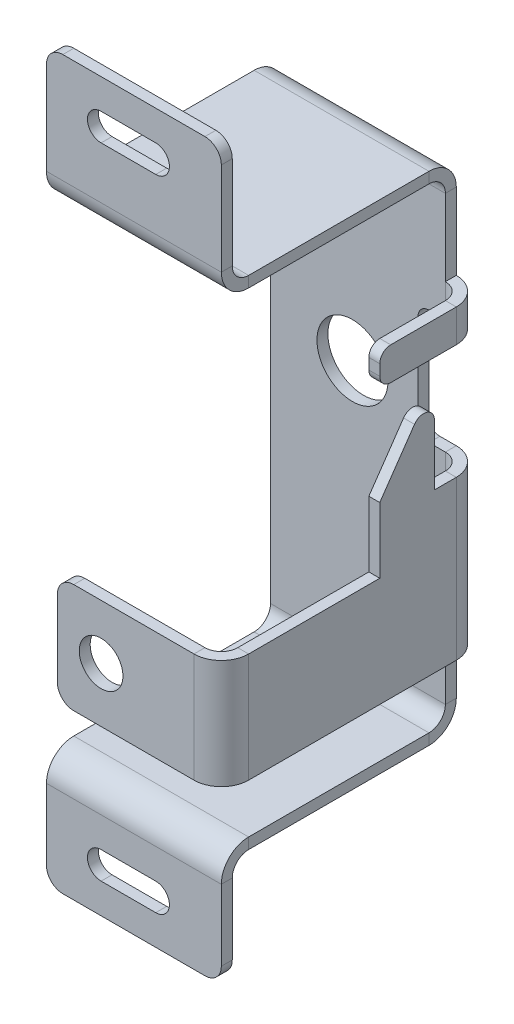
SolidWorks part; units mm, degrees
note: The reader was unsure of these and kept them because the rebuilt part matched: flange length of "Edge-Flange1", "Edge-Flange2", "Edge-Flange3", "Edge-Flange4", "Edge-Flange5", "Edge-Flange6", "Edge-Flange7".
ref_plane "Front Plane" through (0, 0, 0) normal (1, 0, 0) x (0, 1, 0)
ref_plane "Top Plane" through (0, 0, 0) normal (0, 0, 1) x (0, 1, 0)
ref_plane "Right Plane" through (0, 0, 0) normal (0, 1, 0) x (-1, 0, 0)
sketch "Sketch1" plane through (0, 0, 0) normal (0, 0, 1) x (0, 1, 0)
  line L0 (0, 74.7145) -> (0, -84.0142) construction
  line L1 (-132.9432, 0) -> (137.1703, 0) construction
  line L3 (-49, 15) -> (42, 15)
  line L4 (-49, 15) -> (-49, -17)
  line L5 (-49, -17) -> (42, -17)
  line L6 (42, 15) -> (42, -17)
  dimension "D1" = 49
  dimension "D2" = 15
  dimension "D3" = 17
  dimension "D4" = 42
base flange "Base-Flange1" sketch "Sketch1" thickness 2 reverse thickness direction yes parameters "D1"=0.25
edge flange "Edge-Flange1" sketch "Sketch8" flange angle 90 flange length 43 flange position material inside bend radius 3 thickness 2 relief rectangular parameters "D6"=10
sketch "Sketch8" plane through (0, -49, 2) normal (0, -1, 0) x (1, 0, 0)
  line L2 (-15, 0) -> (-15, 41)
  line L3 (-15, 41) -> (17, 41)
  line L4 (17, 41) -> (17, 0)
  line L7 (-15, 0) -> (17, 0) construction
  line L8 (-15, 0) -> (17, 0)
bend "EdgeBend1" bend radius 3 bend angle 90 parameters "D5"=1
edge flange "Edge-Flange2" sketch "Sketch11" flange angle 90 flange length 21 flange position material inside bend radius 3 thickness 2 relief rectangular parameters "D6"=10
sketch "Sketch11" plane through (0, -49, 43) normal (0, 0, 1) x (-1, 0, 0)
  line L0 (-17, 0) -> (15, 0) construction
  line L1 (-17, 0) -> (15, 0)
  line L2 (-17, 0) -> (-17, 19)
  line L3 (-17, 19) -> (15, 19)
  line L4 (15, 19) -> (15, 0)
bend "EdgeBend2" bend radius 3 bend angle 90 parameters "D5"=2
fillet "Fillet1" radius 3 2 edges at (-15, -68, 42) (17, -68, 42)
edge flange "Edge-Flange3" sketch "Sketch14" flange angle 90 flange length 43 flange position bend outside bend radius 3 thickness 2 relief rectangular parameters "D6"=10
sketch "Sketch14" plane through (17, 0, 2) normal (1, 0, 0) x (0, 1, 0)
  line L0 (-33, 0) -> (-4, 0)
  line L2 (-33, 0) -> (-33, 41)
  line L3 (-33, 41) -> (-13, 41)
  line L4 (-13, 41) -> (-13, 17)
  line L5 (-44, -2) -> (42, -2) construction
  line L6 (-49, 3) -> (-49, 36) construction
  line L7 (-4, 7) -> (7.0902, 7)
  line L8 (8.2246, 10.6472) -> (-1, 17)
  line L9 (-1, 17) -> (-13, 17)
  line L10 (2, 56.666) -> (2, -14.644) construction
  line L11 (-4, 7) -> (-4, 0)
  line L12 (-44, 0) -> (42, 0) construction
  line L13 (-68, 39) -> (-68, 41) construction
  arc A0 (7.0902, 7) -> (8.2246, 10.6472) centre (7.0902, 9) ccw
  point P1 (9, 8.406)
  dimension "D9" = 2
  dimension "D1" = 43
  dimension "D2" = 16
  dimension "D3" = 20
  dimension "D4" = 6
  dimension "D5" = 10
  dimension "D6" = 13
  dimension "D7" = 10
  dimension "D8" = 9
  dimension "D10" = 70
bend "EdgeBend3" bend radius 3 bend angle 90 parameters "D5"=3
edge flange "Edge-Flange4" sketch "Sketch17" flange angle 90 flange length 30 flange position bend outside bend radius 3 thickness 2 relief rectangular parameters "D6"=10
sketch "Sketch17" plane through (20, 0, 43) normal (0, 0, 1) x (0, 1, 0)
  line L0 (-13, 0) -> (-33, 0) construction
  line L1 (-13, 0) -> (-33, 0)
  line L2 (-33, 0) -> (-33, 25)
  line L3 (-30, 28) -> (-16, 28)
  line L4 (-13, 25) -> (-13, 0)
  line L5 (-13, -2) -> (-33, -2) construction
  arc A0 (-16, 28) -> (-13, 25) centre (-16, 25) cw
  arc A1 (-33, 25) -> (-30, 28) centre (-30, 25) cw
  circle A2 centre (-23, 20) radius 4
  point P13 (-23, 28)
  dimension "D2" = 3
  dimension "D3" = 8
  dimension "D1" = 30
  dimension "D4" = 22
bend "EdgeBend4" bend radius 3 bend angle 90 parameters "D5"=4
sketch "Sketch18" plane through (0, 0, 2) normal (0, 0, 1) x (1, 0, 0)
  line L0 (-15, 42) -> (-15, -44) construction
  line L1 (-12, -68) -> (14, -68) construction
  line L2 (17, -4) -> (14, -4)
  line L3 (12, -2) -> (12, 15)
  line L4 (14, 17) -> (17, 17)
  line L5 (17, -4) -> (17, 42) construction
  line L6 (0, 2) -> (17, 2) construction
  line L7 (17, 17) -> (17, -4)
  circle A0 centre (0, 2) radius 6.5
  arc A1 (12, 15) -> (14, 17) centre (14, 15) cw
  arc A2 (14, -4) -> (12, -2) centre (14, -2) cw
  dimension "D1" = 13
  dimension "D6" = 2
  dimension "D2" = 15
  dimension "D3" = 70
  dimension "D4" = 12
  dimension "D5" = 15
extrude "Cut-Extrude1" cut sketch "Sketch18" against normal blind 10 normal cut yes
edge flange "Edge-Flange5" sketch "Sketch21" flange angle 90 flange length 19 flange position bend outside bend radius 3 thickness 2 relief rectangular parameters "D6"=10
sketch "Sketch21" plane through (17, 0, 2) normal (1, 0, 0) x (0, 1, 0)
  line L2 (17, 0) -> (17, 15)
  line L3 (19, 17) -> (21, 17)
  line L4 (23, 15) -> (23, 0)
  line L7 (17, 0) -> (42, 0) construction
  line L8 (17, 0) -> (23, 0)
  line L9 (42, 0) -> (42, -2) construction
  line L10 (17, -2) -> (42, -2) construction
  arc A0 (21, 17) -> (23, 15) centre (21, 15) cw
  arc A1 (17, 15) -> (19, 17) centre (19, 15) cw
  dimension "D3" = 2
  dimension "D1" = 19
  dimension "D2" = 19
bend "EdgeBend5" bend radius 3 bend angle 90 parameters "D5"=5
edge flange "Edge-Flange6" sketch "Sketch24" flange angle 90 flange length 43 flange position material inside bend radius 3 thickness 2 relief rectangular parameters "D6"=10
sketch "Sketch24" plane through (0, 42, 2) normal (0, 1, 0) x (-1, 0, 0)
  line L0 (-17, 0) -> (15, 0) construction
  line L1 (-17, 0) -> (15, 0)
  line L2 (-17, 0) -> (-17, 41)
  line L3 (-17, 41) -> (15, 41)
  line L4 (15, 41) -> (15, 0)
bend "EdgeBend6" bend radius 3 bend angle 90 parameters "D5"=6
edge flange "Edge-Flange7" sketch "Sketch27" flange angle 90 flange length 25 flange position material inside bend radius 3 thickness 2 relief rectangular parameters "D6"=10
sketch "Sketch27" plane through (0, 42, 43) normal (0, 0, 1) x (1, 0, 0)
  line L0 (-15, 0) -> (17, 0) construction
  line L1 (-15, 0) -> (17, 0)
  line L2 (-15, 0) -> (-15, 20)
  line L3 (-12, 23) -> (14, 23)
  line L4 (17, 20) -> (17, 0)
  line L5 (-5, 15) -> (5, 15) construction
  line L6 (-5, 17.5) -> (5, 17.5)
  line L7 (-5, 12.5) -> (5, 12.5)
  arc A0 (14, 23) -> (17, 20) centre (14, 20) cw
  arc A1 (-15, 20) -> (-12, 23) centre (-12, 20) cw
  circle A2 centre (0, -40) radius 6.5 construction
  arc A3 (-5, 17.5) -> (-5, 12.5) centre (-5, 15) ccw
  arc A4 (5, 12.5) -> (5, 17.5) centre (5, 15) ccw
  point P12 (0, 15)
  dimension "D1" = 3
  dimension "D2" = 63
  dimension "D4" = 2.5
  dimension "D3" = 10
  dimension "D5" = 15
  dimension "D6" = 8
bend "EdgeBend7" bend radius 3 bend angle 90 parameters "D5"=7
sketch "Sketch28" plane through (0, 0, 43) normal (0, 0, 1) x (1, 0, 0)
  line L0 (-5, -60) -> (5, -60) construction
  line L1 (-5, -57.5) -> (5, -57.5)
  line L2 (-5, -62.5) -> (5, -62.5)
  line L3 (-12, -68) -> (14, -68) construction
  line L4 (-15, -52) -> (-15, -65) construction
  arc A0 (-5, -57.5) -> (-5, -62.5) centre (-5, -60) ccw
  arc A1 (5, -62.5) -> (5, -57.5) centre (5, -60) ccw
  point P2 (0, -60)
  dimension "D2" = 2.5
  dimension "D1" = 10
  dimension "D3" = 8
  dimension "D4" = 15
extrude "Cut-Extrude2" cut sketch "Sketch28" against normal blind 10 normal cut yes
sketch "Bend-Lines1" [suppressed] plane through (0, 0, 0) normal (0, 1, 0) x (1, 0, 0)
sketch "Bounding-Box1" [suppressed] plane through (0, 0, 0) normal (0, 1, 0) x (1, 0, 0)
sheet metal parameters "Sheet-Metal1" thickness 2 parameters "D1"=0.25
flat pattern "Flat-Pattern1" [suppressed]
sketch "Bend-Lines2" plane through (0, 0, 0) normal (0, 1, 0) x (1, 0, 0)
sketch3d "Bounding-Box2" [suppressed]
  line L0 (17, 42, 0) -> (17, -67, 0) construction
  line L1 (-15, 42, 0) -> (-15, -67, 0) construction
  line L2 (17, 42, 0) -> (-15, 42, 0) construction
  line L3 (17, -67, 0) -> (-15, -67, 0) construction
sheet metal parameters "Sheet-Metal2" thickness 2 parameters "D1"=0.25
flat pattern "Flat-Pattern1"
sketch "Bend-Lines2" plane through (0, 0, 0) normal (0, 0, -1) x (-1, 0, 0)
  line L0 (-17, -65.1416) -> (15, -65.1416) construction
  line L1 (-17, -65.1416) -> (15, -65.1416) construction
sketch3d "Bounding-Box2" [suppressed]
  line L0 (-17, 42, 0) -> (-17, -106.2832, 0) construction
  line L1 (15, 42, 0) -> (15, -106.2832, 0) construction
  line L2 (-17, 42, 0) -> (15, 42, 0) construction
  line L3 (-17, -106.2832, 0) -> (15, -106.2832, 0) construction
bend of the flat pattern "Flatten-<EdgeBend1>1"
sheet metal parameters "Sheet-Metal3" thickness 2 parameters "D1"=0.25
flat pattern "Flat-Pattern1"
sketch "Bend-Lines2" plane through (0, 0, 0) normal (0, 0, -1) x (-1, 0, 0)
  line L0 (-17, -47.1416) -> (15, -47.1416) construction
  line L1 (-17, -47.1416) -> (15, -47.1416) construction
  line L2 (-17, -86.4248) -> (15, -86.4248) construction
  line L3 (-17, -86.4248) -> (15, -86.4248) construction
sketch3d "Bounding-Box2" [suppressed]
  line L0 (-17, 42, 0) -> (-17, -105.5664, 0) construction
  line L1 (15, 42, 0) -> (15, -105.5664, 0) construction
  line L2 (-17, 42, 0) -> (15, 42, 0) construction
  line L3 (-17, -105.5664, 0) -> (15, -105.5664, 0) construction
bend of the flat pattern "Flatten-<EdgeBend1>1"
bend of the flat pattern "Flatten-<EdgeBend2>1"
sheet metal parameters "Sheet-Metal4" thickness 2 parameters "D1"=0.25
flat pattern "Flat-Pattern1"
sketch "Bend-Lines2" plane through (0, 0, 0) normal (0, 0, -1) x (-1, 0, 0)
  line L0 (-17, -47.1416) -> (15, -47.1416) construction
  line L1 (-17, -47.1416) -> (15, -47.1416) construction
  line L2 (-17, -86.4248) -> (15, -86.4248) construction
  line L3 (-17, -86.4248) -> (15, -86.4248) construction
  line L4 (-20.1416, -6) -> (-20.1416, -33) construction
  line L5 (-20.1416, -6) -> (-20.1416, -33) construction
sketch3d "Bounding-Box2" [suppressed]
  line L0 (-61.2832, 42, 0) -> (-61.2832, -105.5664, 0) construction
  line L1 (15, 42, 0) -> (15, -105.5664, 0) construction
  line L2 (-61.2832, 42, 0) -> (15, 42, 0) construction
  line L3 (-61.2832, -105.5664, 0) -> (15, -105.5664, 0) construction
bend of the flat pattern "Flatten-<EdgeBend1>1"
bend of the flat pattern "Flatten-<EdgeBend2>1"
bend of the flat pattern "Flatten-<EdgeBend3>1"
sheet metal parameters "Sheet-Metal5" thickness 2 parameters "D1"=0.25
flat pattern "Flat-Pattern1"
sketch "Bend-Lines2" plane through (0, 0, 0) normal (0, 0, -1) x (-1, 0, 0)
  line L0 (-17, -47.1416) -> (15, -47.1416) construction
  line L1 (-17, -47.1416) -> (15, -47.1416) construction
  line L2 (-17, -86.4248) -> (15, -86.4248) construction
  line L3 (-17, -86.4248) -> (15, -86.4248) construction
  line L4 (-20.1416, -4) -> (-20.1416, -33) construction
  line L5 (-20.1416, -4) -> (-20.1416, -33) construction
  line L6 (-64.4248, -13) -> (-64.4248, -33) construction
  line L7 (-64.4248, -13) -> (-64.4248, -33) construction
sketch3d "Bounding-Box2" [suppressed]
  line L0 (-92.5664, 42, 0) -> (-92.5664, -105.5664, 0) construction
  line L1 (15, 42, 0) -> (15, -105.5664, 0) construction
  line L2 (-92.5664, 42, 0) -> (15, 42, 0) construction
  line L3 (-92.5664, -105.5664, 0) -> (15, -105.5664, 0) construction
bend of the flat pattern "Flatten-<EdgeBend1>1"
bend of the flat pattern "Flatten-<EdgeBend2>1"
bend of the flat pattern "Flatten-<EdgeBend3>1"
bend of the flat pattern "Flatten-<EdgeBend4>1"
sheet metal parameters "Sheet-Metal6" thickness 2 parameters "D1"=0.25
flat pattern "Flat-Pattern1"
sketch "Bend-Lines2" plane through (0, 0, 0) normal (0, 0, -1) x (-1, 0, 0)
  line L0 (-17, -47.1416) -> (15, -47.1416) construction
  line L1 (-17, -47.1416) -> (15, -47.1416) construction
  line L2 (-17, -86.4248) -> (15, -86.4248) construction
  line L3 (-17, -86.4248) -> (15, -86.4248) construction
  line L4 (-20.1416, -4) -> (-20.1416, -33) construction
  line L5 (-20.1416, -4) -> (-20.1416, -33) construction
  line L6 (-64.4248, -13) -> (-64.4248, -33) construction
  line L7 (-64.4248, -13) -> (-64.4248, -33) construction
sketch3d "Bounding-Box2" [suppressed]
  line L0 (-92.5664, 42, 0) -> (-92.5664, -105.5664, 0) construction
  line L1 (15, 42, 0) -> (15, -105.5664, 0) construction
  line L2 (-92.5664, 42, 0) -> (15, 42, 0) construction
  line L3 (-92.5664, -105.5664, 0) -> (15, -105.5664, 0) construction
bend of the flat pattern "Flatten-<EdgeBend1>1"
bend of the flat pattern "Flatten-<EdgeBend2>1"
bend of the flat pattern "Flatten-<EdgeBend3>1"
bend of the flat pattern "Flatten-<EdgeBend4>1"
sheet metal parameters "Sheet-Metal7" thickness 2 parameters "D1"=0.25
flat pattern "Flat-Pattern1"
sketch "Bend-Lines2" plane through (0, 0, 0) normal (0, 0, -1) x (-1, 0, 0)
  line L0 (-17, -47.1416) -> (15, -47.1416) construction
  line L1 (-17, -47.1416) -> (15, -47.1416) construction
  line L2 (-17, -86.4248) -> (15, -86.4248) construction
  line L3 (-17, -86.4248) -> (15, -86.4248) construction
  line L4 (-20.1416, -4) -> (-20.1416, -33) construction
  line L5 (-20.1416, -4) -> (-20.1416, -33) construction
  line L6 (-64.4248, -13) -> (-64.4248, -33) construction
  line L7 (-64.4248, -13) -> (-64.4248, -33) construction
  line L8 (-20.1416, 23) -> (-20.1416, 17) construction
  line L9 (-20.1416, 23) -> (-20.1416, 17) construction
sketch3d "Bounding-Box2" [suppressed]
  line L0 (-92.5664, 42, 0) -> (-92.5664, -105.5664, 0) construction
  line L1 (15, 42, 0) -> (15, -105.5664, 0) construction
  line L2 (-92.5664, 42, 0) -> (15, 42, 0) construction
  line L3 (-92.5664, -105.5664, 0) -> (15, -105.5664, 0) construction
bend of the flat pattern "Flatten-<EdgeBend1>1"
bend of the flat pattern "Flatten-<EdgeBend2>1"
bend of the flat pattern "Flatten-<EdgeBend3>1"
bend of the flat pattern "Flatten-<EdgeBend4>1"
bend of the flat pattern "Flatten-<EdgeBend5>1"
sheet metal parameters "Sheet-Metal8" thickness 2 parameters "D1"=0.25
flat pattern "Flat-Pattern1"
sketch "Bend-Lines2" plane through (0, 0, 0) normal (0, 0, -1) x (-1, 0, 0)
  line L0 (-17, -47.1416) -> (15, -47.1416) construction
  line L1 (-17, -47.1416) -> (15, -47.1416) construction
  line L2 (-17, -86.4248) -> (15, -86.4248) construction
  line L3 (-17, -86.4248) -> (15, -86.4248) construction
  line L4 (-20.1416, -4) -> (-20.1416, -33) construction
  line L5 (-20.1416, -4) -> (-20.1416, -33) construction
  line L6 (-64.4248, -13) -> (-64.4248, -33) construction
  line L7 (-64.4248, -13) -> (-64.4248, -33) construction
  line L8 (-20.1416, 23) -> (-20.1416, 17) construction
  line L9 (-20.1416, 23) -> (-20.1416, 17) construction
  line L10 (15, 40.1416) -> (-17, 40.1416) construction
  line L11 (15, 40.1416) -> (-17, 40.1416) construction
sketch3d "Bounding-Box2" [suppressed]
  line L0 (-92.5664, 81.2832, 0) -> (-92.5664, -105.5664, 0) construction
  line L1 (15, 81.2832, 0) -> (15, -105.5664, 0) construction
  line L2 (-92.5664, 81.2832, 0) -> (15, 81.2832, 0) construction
  line L3 (-92.5664, -105.5664, 0) -> (15, -105.5664, 0) construction
bend of the flat pattern "Flatten-<EdgeBend1>1"
bend of the flat pattern "Flatten-<EdgeBend2>1"
bend of the flat pattern "Flatten-<EdgeBend3>1"
bend of the flat pattern "Flatten-<EdgeBend4>1"
bend of the flat pattern "Flatten-<EdgeBend5>1"
bend of the flat pattern "Flatten-<EdgeBend6>1"
sheet metal parameters "Sheet-Metal9" thickness 2 parameters "D1"=0.25
flat pattern "Flat-Pattern1"
sketch "Bend-Lines2" plane through (0, 0, 0) normal (0, 0, -1) x (-1, 0, 0)
  line L0 (-17, -47.1416) -> (15, -47.1416) construction
  line L1 (-17, -47.1416) -> (15, -47.1416) construction
  line L2 (-17, -86.4248) -> (15, -86.4248) construction
  line L3 (-17, -86.4248) -> (15, -86.4248) construction
  line L4 (-20.1416, -4) -> (-20.1416, -33) construction
  line L5 (-20.1416, -4) -> (-20.1416, -33) construction
  line L6 (-64.4248, -13) -> (-64.4248, -33) construction
  line L7 (-64.4248, -13) -> (-64.4248, -33) construction
  line L8 (-20.1416, 23) -> (-20.1416, 17) construction
  line L9 (-20.1416, 23) -> (-20.1416, 17) construction
  line L10 (15, 40.1416) -> (-17, 40.1416) construction
  line L11 (15, 40.1416) -> (-17, 40.1416) construction
  line L12 (15, 79.4248) -> (-17, 79.4248) construction
  line L13 (15, 79.4248) -> (-17, 79.4248) construction
sketch3d "Bounding-Box2" [suppressed]
  line L0 (-92.5664, -105.5664, 0) -> (-92.5664, 102.5664, 0) construction
  line L1 (15, -105.5664, 0) -> (15, 102.5664, 0) construction
  line L2 (-92.5664, -105.5664, 0) -> (15, -105.5664, 0) construction
  line L3 (-92.5664, 102.5664, 0) -> (15, 102.5664, 0) construction
bend of the flat pattern "Flatten-<EdgeBend1>1"
bend of the flat pattern "Flatten-<EdgeBend2>1"
bend of the flat pattern "Flatten-<EdgeBend3>1"
bend of the flat pattern "Flatten-<EdgeBend4>1"
bend of the flat pattern "Flatten-<EdgeBend5>1"
bend of the flat pattern "Flatten-<EdgeBend6>1"
bend of the flat pattern "Flatten-<EdgeBend7>1"
sheet metal parameters "Sheet-Metal10" thickness 2 parameters "D1"=0.25
flat pattern "Flat-Pattern1"
sketch "Bend-Lines2" plane through (0, 0, 0) normal (0, 0, -1) x (-1, 0, 0)
  line L0 (-17, -47.1416) -> (15, -47.1416) construction
  line L1 (-17, -47.1416) -> (15, -47.1416) construction
  line L2 (-17, -86.4248) -> (15, -86.4248) construction
  line L3 (-17, -86.4248) -> (15, -86.4248) construction
  line L4 (-20.1416, -4) -> (-20.1416, -33) construction
  line L5 (-20.1416, -4) -> (-20.1416, -33) construction
  line L6 (-64.4248, -13) -> (-64.4248, -33) construction
  line L7 (-64.4248, -13) -> (-64.4248, -33) construction
  line L8 (-20.1416, 23) -> (-20.1416, 17) construction
  line L9 (-20.1416, 23) -> (-20.1416, 17) construction
  line L10 (15, 40.1416) -> (-17, 40.1416) construction
  line L11 (15, 40.1416) -> (-17, 40.1416) construction
  line L12 (15, 79.4248) -> (-17, 79.4248) construction
  line L13 (15, 79.4248) -> (-17, 79.4248) construction
sketch3d "Bounding-Box2" [suppressed]
  line L0 (-92.5664, -105.5664, 0) -> (-92.5664, 102.5664, 0) construction
  line L1 (15, -105.5664, 0) -> (15, 102.5664, 0) construction
  line L2 (-92.5664, -105.5664, 0) -> (15, -105.5664, 0) construction
  line L3 (-92.5664, 102.5664, 0) -> (15, 102.5664, 0) construction
bend of the flat pattern "Flatten-<EdgeBend1>1"
bend of the flat pattern "Flatten-<EdgeBend2>1"
bend of the flat pattern "Flatten-<EdgeBend3>1"
bend of the flat pattern "Flatten-<EdgeBend4>1"
bend of the flat pattern "Flatten-<EdgeBend5>1"
bend of the flat pattern "Flatten-<EdgeBend6>1"
bend of the flat pattern "Flatten-<EdgeBend7>1"
